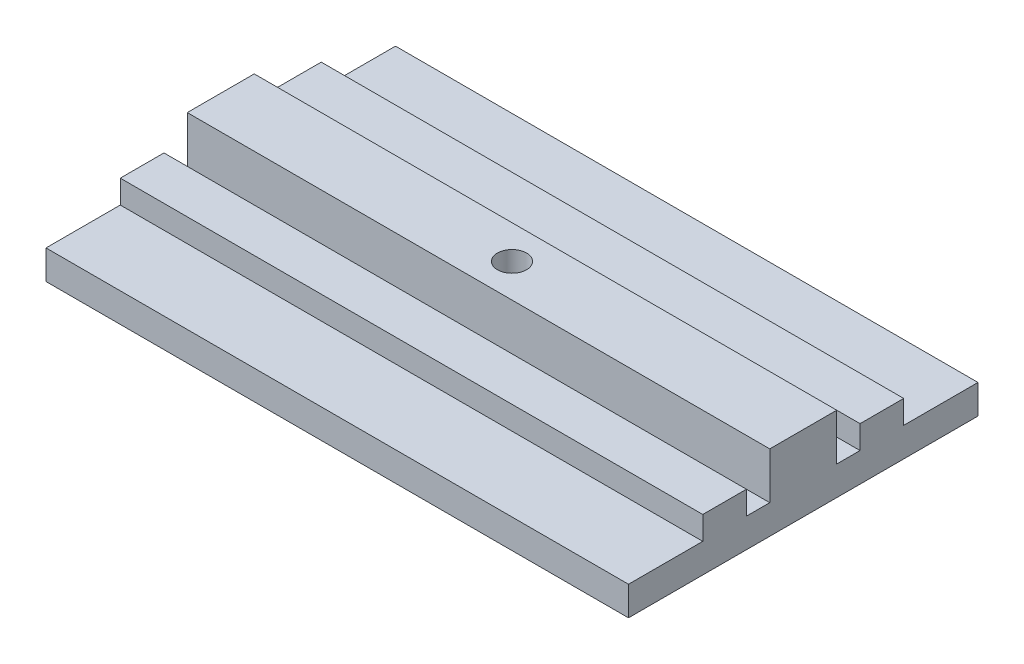
SolidWorks part; units mm, degrees
ref_plane "Front Plane" through (0, 0, 0) normal (0, 0, 1) x (1, 0, 0)
ref_plane "Top Plane" through (0, 0, 0) normal (0, 1, 0) x (1, 0, 0)
ref_plane "Right Plane" through (0, 0, 0) normal (1, 0, 0) x (0, 0, -1)
sketch "Sketch1" plane through (0, 0, 0) normal (0, 1, 0) x (1, 0, 0)
  line L1 (-100, -60) -> (100, -60)
  line L2 (-100, -60) -> (-100, 60)
  line L3 (-100, 60) -> (100, 60)
  line L4 (100, -60) -> (100, 60)
  line L5 (-100, -60) -> (100, 60) construction
  line L6 (-100, 60) -> (100, -60) construction
  point P0 (0, 0)
  dimension "D1" = 120
  dimension "D2" = 200
extrude "Boss-Extrude1" add sketch "Sketch1" along normal blind 10
sketch "Sketch2" plane through (0, 10, 0) normal (0, 1, 0) x (1, 0, 0)
  line L0 (0, 60) -> (0, -60) construction
  line L1 (100, 60) -> (-100, 60) construction
  line L2 (-100, -60) -> (100, -60) construction
  line L3 (100, -60) -> (100, 60) construction
  line L4 (-100, 34.499) -> (100, 34.499)
  line L5 (-100, 34.499) -> (-100, 19.499)
  line L6 (-100, 19.499) -> (100, 19.499)
  line L7 (100, 34.499) -> (100, 19.499)
  line L8 (-100, 34.499) -> (100, 19.499) construction
  line L9 (-100, 19.499) -> (100, 34.499) construction
  line L11 (-100, -19.499) -> (100, -19.499)
  line L12 (-100, -19.499) -> (-100, -34.499)
  line L13 (-100, -34.499) -> (100, -34.499)
  line L14 (100, -19.499) -> (100, -34.499)
  line L15 (-100, -19.499) -> (100, -34.499) construction
  line L16 (-100, -34.499) -> (100, -19.499) construction
  point P6 (0, 26.999)
  point P13 (0, -26.999)
  dimension "D1" = 15
  dimension "D2" = 15
  dimension "D3" = 53.998
  dimension "D4" = 26.999
  dimension "D5" = 19.499
extrude "Boss-Extrude2" add sketch "Sketch2" along normal blind 8
sketch "Sketch3" plane through (0, 10, 0) normal (0, 1, 0) x (1, 0, 0)
  circle A0 centre (0, 0) radius 5
  dimension "D1" = 10
extrude "Cut-Extrude1" cut sketch "Sketch3" against normal through all
sketch "Sketch4" plane through (0, 10, 0) normal (0, 1, 0) x (1, 0, 0)
  line L1 (-100, -11.5) -> (100, -11.5)
  line L2 (-100, -11.5) -> (-100, 11.5)
  line L3 (-100, 11.5) -> (100, 11.5)
  line L4 (100, -11.5) -> (100, 11.5)
  line L5 (-100, -11.5) -> (100, 11.5) construction
  line L6 (-100, 11.5) -> (100, -11.5) construction
  point P0 (0, 0)
  dimension "D1" = 200
  dimension "D2" = 23
extrude "Boss-Extrude4" add sketch "Sketch4" along normal blind 16 contours L3 L4 L1 L2
extrude "Cut-Extrude2" cut sketch "Sketch3<2>" against normal through all both and the other way through all
sketch "Sketch3<2>" plane through (0, 10, 0) normal (0, 1, 0) x (1, 0, 0) same geometry as "Sketch3"
